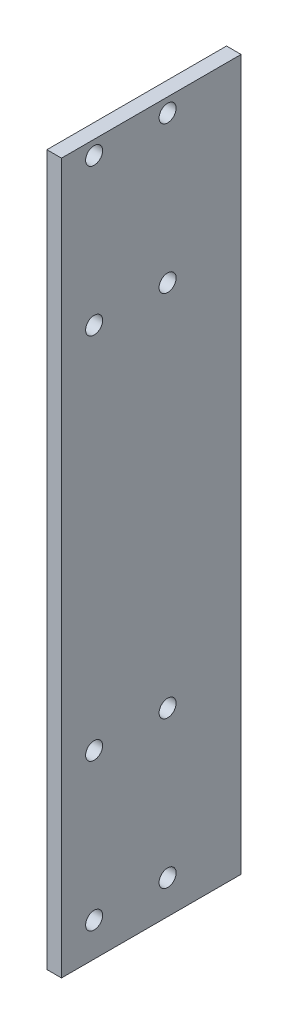
SolidWorks part; units mm, degrees
ref_plane "Front" through (0, 0, 0) normal (0, 0, 1) x (1, 0, 0)
ref_plane "Top" through (0, 0, 0) normal (0, 1, 0) x (1, 0, 0)
ref_plane "Right" through (0, 0, 0) normal (1, 0, 0) x (0, 0, -1)
ref_axis "side-side" through (80.9, 0, 0) along (-1, 0, 0)
ref_axis "up-down" through (0, 50, 0) along (0, -1, 0)
ref_axis "front-back" through (0, 0, -80.9) along (0, 0, 1)
sketch "Sketch1" plane through (0, 0, 0) normal (1, 0, 0) x (0, 0, -1)
  line L0 (0, 0) -> (-58.8898, 0) construction
  line L1 (-58.8898, 112.2) -> (5.9451, 112.2) construction
  line L2 (-82, -23.3591) -> (-42.8868, -23.3591)
  line L3 (-82, -23.3591) -> (-82, 131.25)
  line L4 (-82, 131.25) -> (-42.8868, 131.25)
  line L5 (-42.8868, -23.3591) -> (-42.8868, 131.25)
  line L6 (0, 50) -> (0, -50) construction
  line L8 (-58.8898, 16) -> (-58.8898, -16) construction
  line L9 (-58.8898, 128.2) -> (-58.8898, 96.2) construction
  circle A0 centre (-74.8898, -16) radius 1.8542
  circle A1 centre (-58.8898, -16) radius 1.8542
  circle A2 centre (-74.8898, 16) radius 1.8542
  circle A3 centre (-58.8898, 16) radius 1.8542
  circle A4 centre (-74.8898, 128.2) radius 1.8542
  circle A5 centre (-58.8898, 128.2) radius 1.8542
  circle A6 centre (-74.8898, 96.2) radius 1.8542
  circle A7 centre (-58.8898, 96.2) radius 1.8542
  point P6 (0, 0)
  point P7 (0, 0)
  point P16 (0, 0)
  point P19 (0, 0)
  dimension "D2" = 3.7084
  dimension "D6" = 32
  dimension "D1" = 82
  dimension "D3" = 3.05
  dimension "D4" = 112.2
  dimension "D5" = 23.3591
extrude "Boss-Extrude1" add sketch "Sketch1" along normal blind 3.175
